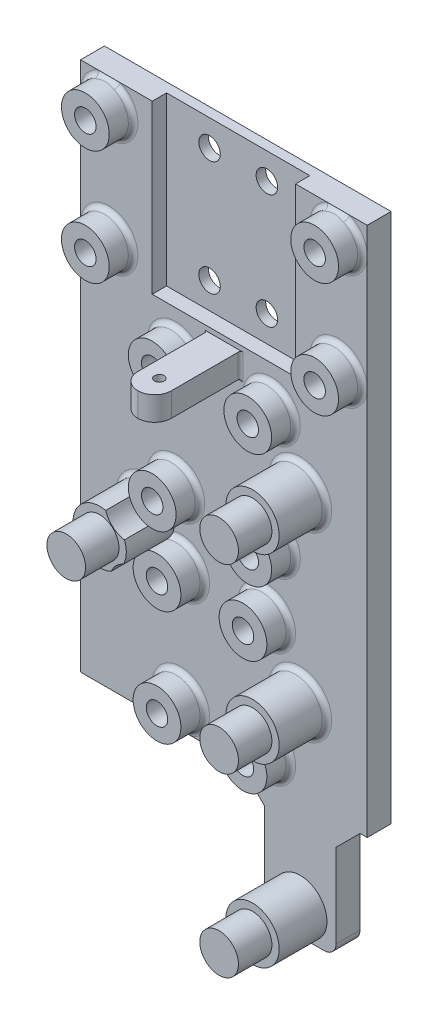
SolidWorks part; units mm, degrees
ref_plane "Front Plane" through (0, 0, 0) normal (0, 0, 1) x (1, 0, 0)
ref_plane "Top Plane" through (0, 0, 0) normal (0, 1, 0) x (1, 0, 0)
ref_plane "Right Plane" through (0, 0, 0) normal (1, 0, 0) x (0, 0, -1)
sketch "Sketch1" plane through (0, 0, 0) normal (0, 0, 1) x (1, 0, 0)
  line L0 (6, -5.5) -> (0, -5.5) construction
  line L5 (0, 0) -> (30, 0)
  line L6 (0, 0) -> (0, -35)
  line L7 (0, -35) -> (30, -35)
  line L8 (30, 0) -> (30, -35)
  line L9 (30, 0) -> (60, 0)
  line L10 (30, 0) -> (30, -35)
  line L27 (30, -35) -> (60, -35)
  line L28 (60, 0) -> (60, -35)
  line L29 (15, -35) -> (45, -35)
  line L30 (15, -35) -> (15, -38.5)
  line L31 (15, -76) -> (45, -76)
  line L32 (15, -38.5) -> (45, -38.5)
  line L41 (45, -35) -> (45, -38.5)
  line L42 (15, -38.5) -> (45, -38.5)
  line L43 (15, -38.5) -> (15, -72.5)
  line L44 (15, -72.5) -> (45, -72.5)
  line L45 (45, -38.5) -> (45, -72.5)
  line L46 (15, -72.5) -> (45, -72.5)
  line L47 (15, -72.5) -> (15, -76)
  line L48 (15, -76) -> (45, -76)
  line L49 (45, -72.5) -> (45, -76)
  line L50 (15, -76) -> (15, -111)
  line L51 (15, -111) -> (45, -111)
  line L52 (45, -76) -> (45, -111)
  line L53 (24, -29.5) -> (30, -29.5) construction
  line L54 (24, -29.5) -> (24, -35) construction
  line L55 (6, -5.5) -> (6, 0) construction
  line L56 (20, -43.5) -> (15, -43.5) construction
  line L57 (20, -43.5) -> (20, -38.5) construction
  line L58 (40, -67.5) -> (45, -67.5) construction
  line L59 (40, -67.5) -> (40, -72.5) construction
  line L60 (21, -81.5) -> (21, -76) construction
  line L61 (21, -81.5) -> (15, -81.5) construction
  line L62 (39, -105.5) -> (45, -105.5) construction
  line L63 (39, -105.5) -> (39, -111) construction
  circle A0 centre (6, -5.5) radius 2.25
  circle A1 centre (24, -5.5) radius 2.25
  circle A2 centre (6, -29.5) radius 2.25
  circle A3 centre (24, -29.5) radius 2.25
  circle A4 centre (20, -43.5) radius 2.25
  circle A5 centre (40, -43.5) radius 2.25
  circle A6 centre (20, -67.5) radius 2.25
  circle A7 centre (40, -67.5) radius 2.25
  circle A8 centre (21, -81.5) radius 2.25
  circle A9 centre (39, -81.5) radius 2.25
  circle A10 centre (21, -105.5) radius 2.25
  circle A11 centre (39, -105.5) radius 2.25
  circle A12 centre (54, -29.5) radius 2.25
  circle A13 centre (36, -29.5) radius 2.25
  circle A14 centre (36, -5.5) radius 2.25
  circle A15 centre (54, -5.5) radius 2.25
  point P16 (60, -17.5)
  point P17 (30, -35)
  point P18 (45, -55.5)
  point P19 (45, -93.5)
  dimension "D4" = 35
  dimension "D5" = 30
  dimension "D12" = 24
  dimension "D9" = 4.5
  dimension "D1" = 30
  dimension "D2" = 35
  dimension "D3" = 30
  dimension "D6" = 34
  dimension "D7" = 38
  dimension "D8" = 38
  dimension "D10" = 24
  dimension "D11" = 18
  dimension "D13" = 20
  dimension "D14" = 24
  dimension "D15" = 18
extrude "Boss-Extrude1" add sketch "Sketch1" along normal blind 5 contours L8 L5 L6 L7 A3 A2 A1 A0 | L28 L9 L8 L27 A14 A12 A13 A15 | L45 L32 L43 L44 A7 A6 A5 A4 | L41 L27 L7 L30 L32 | L49 L44 L47 L31 | L52 L31 L50 L51 A11 A10 A9 A8 region at (15, -17.5, 0) region at (45, -17.5, 0) region at (30, -36.75, 0) region at (30, -55.5, 0) region at (30, -74.25, 0) region at (30, -93.5, 0)
sketch "Sketch2" plane through (0, 0, 5) normal (0, 0, 1) x (1, 0, 0)
  line L0 (15, -111) -> (45, -111) construction
  line L3 (38.5, -111) -> (53.5, -111)
  line L4 (38.5, -111) -> (38.5, -136)
  line L5 (38.5, -136) -> (53.5, -136)
  line L6 (53.5, -111) -> (53.5, -136)
  line L7 (38.5, -111) -> (53.5, -136) construction
  line L8 (38.5, -136) -> (53.5, -111) construction
  point P2 (30, -111)
  point P3 (46, -136)
  point P5 (46, -123.5)
  dimension "D1" = 25
  dimension "D2" = 15
  dimension "D3" = 16
extrude "Boss-Extrude2" add sketch "Sketch2" against normal up to surface (5 mm away) up to face at (30, -45.25, 0)
sketch "Sketch7" plane through (0, 0, 5) normal (0, 0, 1) x (1, 0, 0)
  line L9 (0, -35) -> (15, -35)
  line L10 (0, -35) -> (0, -111)
  line L11 (0, -111) -> (15, -111)
  line L12 (15, -35) -> (15, -111)
  line L13 (45, -111) -> (60, -111)
  line L14 (45, -111) -> (45, -35)
  line L15 (45, -35) -> (60, -35)
  line L16 (60, -111) -> (60, -35)
  dimension "D1" = 15
extrude "Boss-Extrude5" add sketch "Sketch7" against normal up to surface (5 mm away) up to face at (35.3333, -71.3333, 0)
sketch "Sketch3" plane through (0, 0, 5) normal (0, 0, 1) x (1, 0, 0)
  line L0 (0, -36.5) -> (60, -36.5) construction
  line L2 (0, 0) -> (0, -111) construction
  line L3 (60, 0) -> (60, -111) construction
  line L5 (38.5, -136) -> (53.5, -136) construction
  line L6 (46, -130.425) -> (46, -136) construction
  line L7 (24, -29.5) -> (36, -29.5) construction
  line L8 (30, -29.5) -> (30, -36.5) construction
  line L9 (20, -43.5) -> (40, -43.5) construction
  line L11 (30, -36.5) -> (30, -43.5) construction
  line L12 (21, -81.5) -> (39, -81.5) construction
  line L13 (21, -105.5) -> (39, -105.5) construction
  line L14 (30, -81.5) -> (30, -105.5) construction
  line L15 (60, -93.5) -> (0, -93.5) construction
  line L16 (20, -67.5) -> (40, -67.5) construction
  line L17 (30, -43.5) -> (30, -67.5) construction
  line L18 (60, -55.5) -> (0, -55.5) construction
  line L19 (30, -67.5) -> (30, -81.5) construction
  line L20 (60, -74.5) -> (0, -74.5) construction
  circle A5 centre (46, -130.425) radius 5.575
  circle A10 centre (46, -93.5) radius 5.575
  circle A11 centre (14, -74.5) radius 5.575
  circle A13 centre (46, -55.5) radius 5.575
  point P29 (30, -93.5)
  point P36 (30, -55.5)
  point P51 (30, -74.5)
  dimension "D1" = 11.15
  dimension "D2" = 16
  dimension "D4" = 16
  dimension "D3" = 16
extrude "Boss-Extrude3" add sketch "Sketch3" along normal blind 10
sketch "Sketch6" plane through (0, 0, 15) normal (0, 0, 1) x (1, 0, 0)
  circle A0 centre (46, -130.425) radius 4.05
  circle A6 centre (46, -93.5) radius 4.05
  circle A7 centre (14, -74.5) radius 4.05
  circle A8 centre (46, -55.5) radius 4.05
  dimension "D1" = 8.1
extrude "Boss-Extrude4" add sketch "Sketch6" along normal blind 7
sketch "Sketch8" plane through (0, 0, 5) normal (0, 0, 1) x (1, 0, 0)
  line L0 (0, 0) -> (60, 0) construction
  line L1 (15, 0) -> (45, 0)
  line L2 (15, 0) -> (15, -35)
  line L3 (15, -35) -> (45, -35)
  line L4 (45, 0) -> (45, -35)
  dimension "D1" = 15
  dimension "D2" = 15
  dimension "D3" = 35
extrude "Cut-Extrude1" cut sketch "Sketch8" against normal blind 3
sketch "Sketch9" plane through (0, 0, 5) normal (0, 0, 1) x (1, 0, 0)
  circle A0 centre (21, -105.5) radius 5
  circle A1 centre (39, -105.5) radius 5
  circle A2 centre (39, -81.5) radius 5
  circle A3 centre (21, -81.5) radius 5
  circle A4 centre (20, -67.5) radius 5
  circle A5 centre (40, -67.5) radius 5
  circle A6 centre (20, -43.5) radius 5
  circle A7 centre (40, -43.5) radius 5
  circle A8 centre (54, -29.5) radius 5
  circle A9 centre (54, -5.5) radius 5
  circle A10 centre (6, -29.5) radius 5
  circle A11 centre (6, -5.5) radius 5
  circle M18 centre (6, -29.5) radius 2.25
  circle M19 centre (6, -5.5) radius 2.25
  circle M20 centre (54, -29.5) radius 2.25
  circle M21 centre (54, -5.5) radius 2.25
  circle M22 centre (40, -67.5) radius 2.25
  circle M23 centre (20, -67.5) radius 2.25
  circle M24 centre (40, -43.5) radius 2.25
  circle M25 centre (20, -43.5) radius 2.25
  circle M26 centre (39, -105.5) radius 2.25
  circle M27 centre (21, -105.5) radius 2.25
  circle M28 centre (39, -81.5) radius 2.25
  circle M29 centre (21, -81.5) radius 2.25
  dimension "D1" = 10
extrude "Boss-Extrude6" add sketch "Sketch9" along normal blind 5 contours A0 M27 | A1 M26 | A3 M29 | A2 M28 | A5 M22 | A4 M23 | A6 M25 | A7 M24 | A8 M20 | A10 M18 | A11 M19 | A9 M21 region at (16.1414, -105.5, 5) region at (34.1414, -105.5, 5) region at (34.1414, -81.5, 5) region at (16.1414, -81.5, 5) region at (15.1414, -67.5, 5) region at (35.1414, -67.5, 5) region at (15.1414, -43.5, 5) region at (35.1414, -43.5, 5) region at (49.1414, -29.5, 5) region at (49.1414, -5.5, 5) region at (1.1414, -29.5, 5) region at (1.1414, -5.5, 5)
fillet "Fillet2" radius 1 15 edges at (59, -5.5, 5) (11, -5.5, 5) (11, -29.5, 5) (59, -29.5, 5) (45, -43.5, 5) (25, -43.5, 5) (51.575, -55.5, 5) (23.254, -63.7037, 5) (45, -67.5, 5) (51.575, -93.5, 5) (24.5355, -85.0355, 5) (44, -81.5, 5) (44, -105.5, 5) (26, -105.5, 5) (8.4585, -75.1104, 5)
chamfer "Chamfer1" distance 5 angle 45 2 edges at (38.5, -111, 2.5606) (53.5, -111, 2.5)
fillet "Fillet1" radius 2.5 2 edges at (53.5, -136, 2.5) (38.5, -136, 2.5)
sketch "Sketch11" plane through (0, 0, 10) normal (0, 0, 1) x (1, 0, 0)
  circle A0 centre (20, -67.5) radius 5
  circle A1 centre (21, -81.5) radius 5
  arc A2 (19.1772, -72.4318) -> (15.252, -69.0674) centre (20, -67.5) ccw construction
  circle A3 centre (21, -81.5) radius 5 construction
extrude "Cut-Extrude2" cut sketch "Sketch11" along normal through all
sketch "Sketch12" plane through (0, 0, 5) normal (0, 0, 1) x (1, 0, 0)
  line L1 (26.5, -36) -> (33.5, -36)
  line L2 (26.5, -36) -> (26.5, -41)
  line L3 (26.5, -41) -> (33.5, -41)
  line L4 (33.5, -36) -> (33.5, -41)
  line L5 (30, -35) -> (30, -36) construction
  line L6 (15, -35) -> (45, -35) construction
  dimension "D1" = 7
  dimension "D2" = 5
  dimension "D3" = 1
extrude "Boss-Extrude7" add sketch "Sketch12" along normal blind 18
sketch "Sketch13" plane through (0, -41, 0) normal (0, -1, 0) x (1, 0, 0)
  line L0 (30, 5) -> (30, 18.5) construction
  line L1 (26.5, 5) -> (33.5, 5) construction
  circle A0 centre (30, 18.5) radius 1
  dimension "D2" = 2
  dimension "D1" = 13.5
extrude "Cut-Extrude3" cut sketch "Sketch13" against normal through all
sketch "Sketch14" plane through (0, 0, 22) normal (0, 0, 1) x (1, 0, 0)
  circle A0 centre (46, -55.5) radius 18.1325 construction
  circle A1 centre (14, -74.5) radius 18.1325 construction
  circle A2 centre (46, -93.5) radius 18.1325 construction
  circle A3 centre (46, -130.425) radius 18 construction
  dimension "D1" = 36
fillet "Fillet3" radius 3.5 2 edges at (33.5, -38.5, 23) (26.5, -38.5, 23)
fillet "Fillet4" radius 0.5 3 edges at (33.5, -38.5, 5) (30, -41, 5) (26.5, -38.5, 5)
